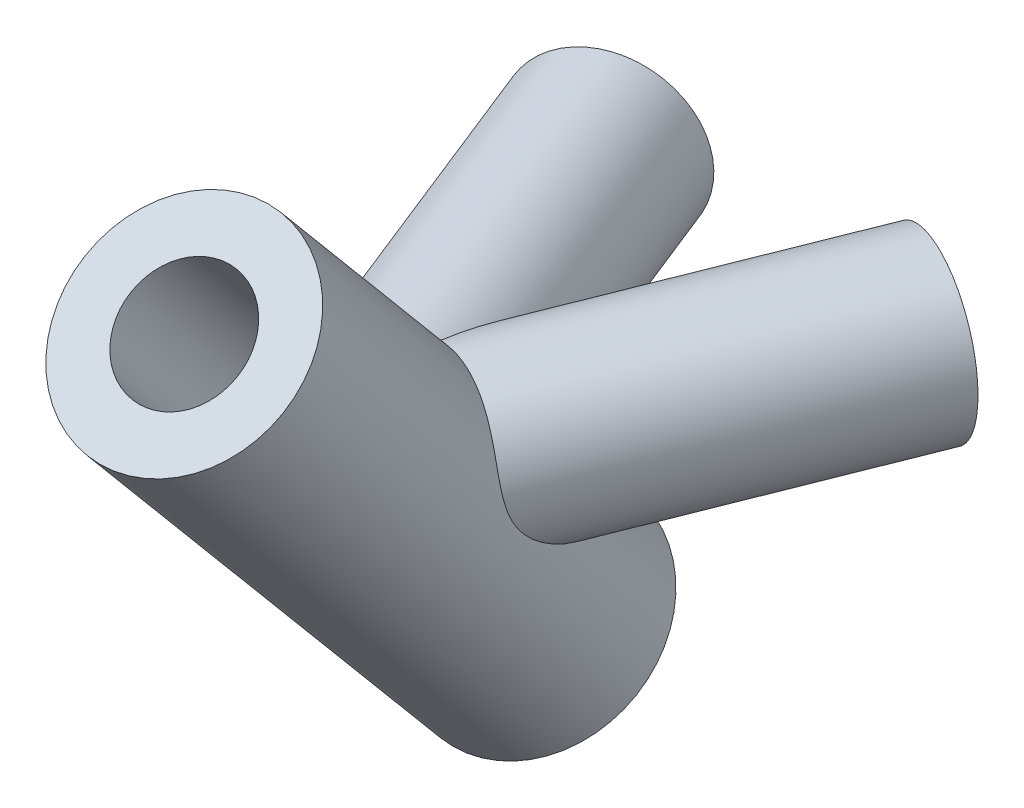
SolidWorks part; units mm, degrees
ref_plane "Front Plane" through (0, 0, 0) normal (0, 0, 1) x (1, 0, 0)
ref_plane "Top Plane" through (0, 0, 0) normal (0, 1, 0) x (1, 0, 0)
ref_plane "Right Plane" through (0, 0, 0) normal (1, 0, 0) x (0, 0, -1)
ref_axis "Axis1" through (-88.99, 0, 0) along (1, 0, 0)
ref_plane "Plane1" through (0, 0, 0) normal (0, 0.766, 0.6428) x (1, 0, 0)
sketch "Sketch1" plane through (0, 0, 0) normal (0, 0.766, 0.6428) x (1, 0, 0)
  circle A0 centre (0, 0) radius 5.08
  dimension "D1" = 10.16
extrude "Boss-Extrude1" add sketch "Sketch1" along normal mid plane 25.4
ref_axis "Axis2" through (0, 14.2935, 0) along (0, -1, 0)
ref_plane "Plane2" through (0, 0, 0) normal (-0.3697, 0, -0.9291) x (0, -1, 0)
sketch "Sketch5" plane through (0, 0, 0) normal (-0.3697, 0, -0.9291) x (0, -1, 0)
  circle A0 centre (0, 0) radius 3.81
  dimension "D1" = 7.62
extrude "Boss-Extrude2" add sketch "Sketch5" along normal blind 20.32
sketch "Sketch6" plane through (-7.5133, 0, -18.88) normal (-0.3697, 0, -0.9291) x (-0.9291, 0, 0.3697)
  circle A0 centre (0, 0) radius 2.7305
  dimension "D1" = 5.461
extrude "Cut-Extrude1" cut sketch "Sketch6" against normal blind 10.16
mirror "Mirror1" about plane through (0, 0, 0) normal (1, 0, 0) of "Cut-Extrude1", "Boss-Extrude2"
sketch "Sketch7" plane through (0, -9.7288, -8.1634) normal (0, -0.766, -0.6428) x (1, 0, 0)
  circle A0 centre (0, 0) radius 2.7305
  dimension "D1" = 5.461
extrude "Cut-Extrude2" cut sketch "Sketch7" against normal up to next
